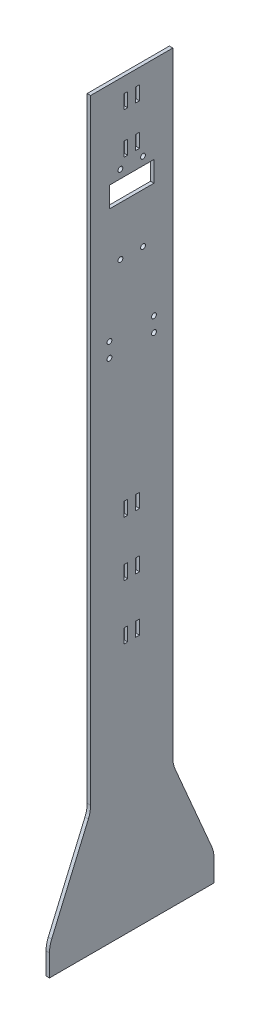
SolidWorks part; units mm, degrees
ref_plane "Front Plane" through (0, 0, 0) normal (0, 0, 1) x (1, 0, 0)
ref_plane "Top Plane" through (0, 0, 0) normal (0, 1, 0) x (1, 0, 0)
ref_plane "Right Plane" through (0, 0, 0) normal (1, 0, 0) x (0, 0, -1)
sketch "Sketch1" plane through (0, 0, 0) normal (1, 0, 0) x (0, 0, -1)
  line L1 (-38.1, 457.2) -> (38.1, 457.2)
  line L2 (-38.1, 457.2) -> (-38.1, -457.2)
  line L3 (-38.1, -457.2) -> (38.1, -457.2)
  line L4 (38.1, 457.2) -> (38.1, -457.2)
  line L5 (-38.1, 457.2) -> (38.1, -457.2) construction
  line L6 (-38.1, -457.2) -> (38.1, 457.2) construction
  point P0 (0, 0)
  dimension "D1" = 914.4
  dimension "D2" = 76.2
extrude "Boss-Extrude1" add sketch "Sketch1" along normal blind 3.175
sketch "Sketch2" plane through (3.175, 0, 0) normal (1, 0, 0) x (0, 0, -1)
  line L0 (-38.1, -457.2) -> (38.1, -457.2) construction
  line L1 (3.722, -204.5335) -> (7.278, -204.5335)
  line L2 (3.722, -204.5335) -> (3.722, -217.4875)
  line L3 (3.722, -217.4875) -> (7.278, -217.4875)
  line L4 (7.278, -204.5335) -> (7.278, -217.4875)
  line L5 (3.722, -204.5335) -> (7.278, -217.4875) construction
  line L6 (3.722, -217.4875) -> (7.278, -204.5335) construction
  point P0 (5.5, -211.0105)
  dimension "D1" = 3.556
  dimension "D2" = 12.954
  dimension "D3" = 239.7125
  dimension "D4" = 3.722
extrude "Cut-Extrude1" cut sketch "Sketch2" against normal through all
mirror "Mirror1" about plane through (0, 0, 0) normal (0, 0, 1) of "Cut-Extrude1"
pattern_linear "LPattern1" count 2 spacing 50.8 along (0, 1, 0) count 2 spacing 50.8 along (0, -1, 0) of "Mirror1"
sketch "Sketch3" plane through (3.175, 0, 0) normal (1, 0, 0) x (0, 0, -1)
  line L0 (7.278, -166.6875) -> (7.278, -153.7335) construction
  line L1 (3.722, 135.1915) -> (7.278, 135.1915)
  line L2 (3.722, 135.1915) -> (3.722, 122.2375)
  line L3 (3.722, 122.2375) -> (7.278, 122.2375)
  line L4 (7.278, 135.1915) -> (7.278, 122.2375)
  line L5 (3.722, 135.1915) -> (7.278, 122.2375) construction
  line L6 (3.722, 122.2375) -> (7.278, 135.1915) construction
  line L7 (7.278, -153.7335) -> (3.722, -153.7335) construction
  line L8 (3.722, -153.7335) -> (3.722, -166.6875) construction
  line L9 (0, 0) -> (0, 52.1648) construction
  line L10 (-3.722, 122.2375) -> (-7.278, 135.1915) construction
  line L11 (-3.722, 135.1915) -> (-7.278, 122.2375) construction
  line L12 (-7.278, 135.1915) -> (-7.278, 122.2375)
  line L13 (-3.722, 122.2375) -> (-7.278, 122.2375)
  line L14 (-3.722, 135.1915) -> (-3.722, 122.2375)
  line L15 (-3.722, 135.1915) -> (-7.278, 135.1915)
  point P0 (5.5, 128.7145)
  point P18 (-5.5, 128.7145)
  dimension "D1" = 275.971
extrude "Cut-Extrude2" cut sketch "Sketch3" against normal through all
pattern_linear "LPattern2" count 2 spacing 38.1 along (0, 1, 0) of "Cut-Extrude2"
sketch "Sketch4" plane through (3.175, 0, 0) normal (1, 0, 0) x (0, 0, -1)
  line L0 (0, -457.2) -> (0, 187.325) construction
  line L1 (-38.1, -457.2) -> (38.1, -457.2) construction
  line L2 (0, 187.325) -> (-38.1, 187.325)
  line L3 (-38.1, 457.2) -> (-38.1, -457.2) construction
  line L4 (-38.1, 187.325) -> (38.1, 187.325)
  line L5 (38.1, -457.2) -> (38.1, 457.2) construction
  line M30 (38.1, -457.2) -> (38.1, 457.2)
  line M31 (38.1, 457.2) -> (-38.1, 457.2)
  line M32 (-38.1, 457.2) -> (-38.1, -457.2)
  dimension "D1" = 644.525
extrude "Cut-Extrude3" cut sketch "Sketch4" against normal through all contours L2 L4 M30 M31 M32 region at (3.175, 322.2625, 0)
sketch "Sketch5" plane through (3.175, 0, 0) normal (1, 0, 0) x (0, 0, -1)
  line L0 (-38.1, -457.2) -> (-38.1, -501.65)
  line L1 (-38.1, -501.65) -> (38.1, -501.65)
  line L2 (38.1, -501.65) -> (38.1, -457.2)
  line L7 (38.1, -457.2) -> (38.1, 187.325)
  line L8 (38.1, 187.325) -> (-38.1, 187.325)
  line L9 (-38.1, 187.325) -> (-38.1, -457.2)
  line L10 (-38.1, -457.2) -> (38.1, -457.2)
  line L14 (-38.1, -457.2) -> (38.1, -457.2)
  dimension "D1" = 44.45
  dimension "D2" = 0
extrude "Boss-Extrude2" add sketch "Sketch5" against normal up to surface (3.175 mm away) up to face at (0, -160.2105, 5.5)
sketch "Sketch6" plane through (3.175, 0, 0) normal (1, 0, 0) x (0, 0, -1)
  line L1 (-20.6375, 106.6318) -> (20.6375, 106.6318)
  line L2 (-20.6375, 106.6318) -> (-20.6375, 87.5818)
  line L4 (20.6375, 106.6318) -> (20.6375, 87.5818)
  line L5 (0, 187.325) -> (0, 38.8722) construction
  line L6 (38.1, 187.325) -> (-38.1, 187.325) construction
  line L7 (-20.6375, 87.5818) -> (20.6375, 87.5818)
  line L8 (-20.6375, 119.3318) -> (20.6375, 119.3318) construction
  point P6 (0, 106.6318)
  dimension "D1" = 19.05
  dimension "D2" = 41.275
  dimension "D3" = 12.7
extrude "Cut-Extrude4" cut sketch "Sketch6" against normal through all contours L7 L4 L1 L2
sketch "Sketch7" plane through (3.175, 0, 0) normal (1, 0, 0) x (0, 0, -1)
  line L0 (-76.2, -501.65) -> (76.2, -501.65)
  line L1 (76.2, -501.65) -> (76.2, -476.25)
  line L2 (76.2, -476.25) -> (38.1, -387.35)
  line L3 (38.1, -501.65) -> (38.1, 187.325) construction
  line L4 (38.1, -387.35) -> (-38.1, -387.35)
  line L5 (-38.1, 187.325) -> (-38.1, -501.65) construction
  line L6 (-38.1, -387.35) -> (-76.2, -476.25)
  line L7 (-76.2, -476.25) -> (-76.2, -501.65)
  line L8 (-38.1, -501.65) -> (38.1, -501.65) construction
  dimension "D1" = 152.4
  dimension "D2" = 38.1
  dimension "D3" = 25.4
  dimension "D4" = 114.3
extrude "Boss-Extrude3" add sketch "Sketch7" against normal blind 3.175
fillet "Fillet1" radius 25.4 4 edges at (1.5875, -476.25, 76.2) (1.5875, -387.35, 38.1) (1.5875, -476.25, -76.2) (1.5875, -387.35, -38.1)
hole_wizard "#8 Clearance Hole1" positions "Sketch8" profile "Sketch9" hole size "#8" standard "ANSI Inch" end condition through all
sketch "Sketch8" plane through (3.175, 0, 0) normal (1, 0, 0) x (0, 0, -1)
  point P0 (10.4775, 41.8618)
  point P3 (-10.4775, 41.8618)
  point P6 (20.6375, -18.8258)
  point P9 (-20.6375, -18.8258)
  point P12 (20.6375, -32.3008)
  point P15 (-20.6375, -32.3008)
  point P19 (10.4775, 114.2518)
  point P22 (-10.4775, 114.2518)
sketch "Sketch9" plane through (3.175, 41.8618, -10.4775) normal (0, 1, 0) x (0, 0, -1)
  line L0 (0, 0) -> (0, 3.175)
  line L1 (0, 3.175) -> (2.2479, 3.175)
  line L2 (2.2479, 3.175) -> (2.2479, 0)
  line L5 (2.2479, 0) -> (0, 0)
  line L11 (0, -6.35) -> (0, 107.95) construction
  dimension "Thru Hole Dia." = 4.4958
  dimension "Thru Hole Depth" = 3.175
